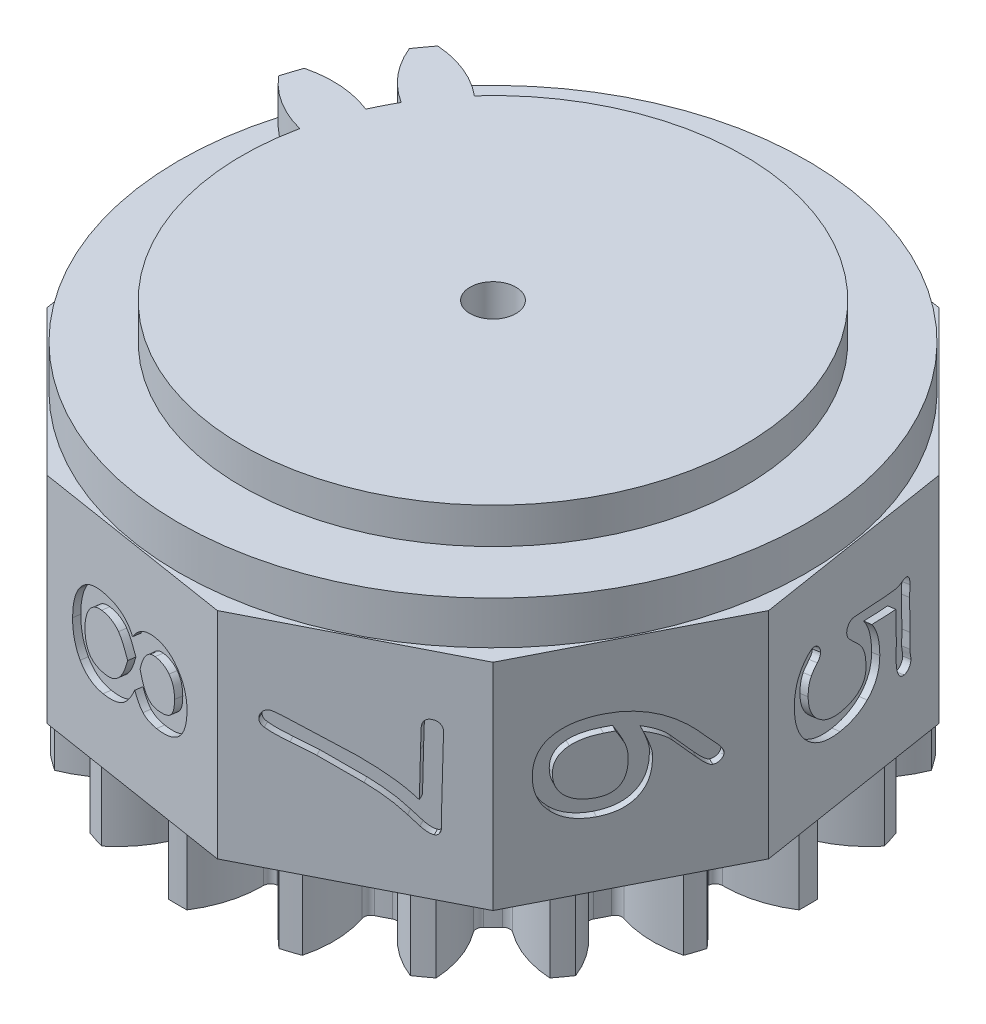
SolidWorks part; units mm, degrees
ref_plane "Front Plane" through (0, 0, 0) normal (0, 0, 1) x (1, 0, 0)
ref_plane "Top Plane" through (0, 0, 0) normal (0, 1, 0) x (1, 0, 0)
ref_plane "Right Plane" through (0, 0, 0) normal (1, 0, 0) x (0, 0, -1)
sketch "Sketch1" plane through (0, 0, 0) normal (0, 1, 0) x (1, 0, 0)
  line L0 (0, 0) -> (0, 59.8949) construction
  line L1 (0, 0) -> (3.1384, 39.8767) construction
  circle A0 centre (0, 0) radius 44
  circle A1 centre (0, 0) radius 37.59 construction
  circle A2 centre (0, 0) radius 40 construction
  circle A3 centre (0, 0) radius 35
  arc A4 (3.6535, 34.8088) -> (0, 45.7006) centre (-11.3105, 35.848) ccw
  arc A5 (-3.6535, 34.8088) -> (0, 45.7006) centre (11.3105, 35.848) cw
  arc A6 (14.2311, 31.9762) -> (14.1222, 43.4638) centre (0.3207, 37.5886) ccw
  arc A7 (7.2819, 34.2341) -> (14.1222, 43.4638) centre (21.8346, 30.5984) cw
  arc A8 (23.4158, 26.0135) -> (26.8621, 36.9725) centre (11.9205, 35.6498) ccw
  arc A9 (17.5044, 30.3084) -> (26.8621, 36.9725) centre (30.2213, 22.3535) cw
  arc A10 (30.3084, 17.5044) -> (36.9725, 26.8621) centre (22.3535, 30.2213) ccw
  arc A11 (26.0135, 23.4158) -> (36.9725, 26.8621) centre (35.6498, 11.9205) cw
  arc A12 (34.2341, 7.2819) -> (43.4638, 14.1222) centre (30.5984, 21.8346) ccw
  arc A13 (31.9762, 14.2311) -> (43.4638, 14.1222) centre (37.5886, 0.3207) cw
  arc A14 (34.8088, -3.6535) -> (45.7006, 0) centre (35.848, 11.3105) ccw
  arc A15 (34.8088, 3.6535) -> (45.7006, 0) centre (35.848, -11.3105) cw
  arc A16 (31.9762, -14.2311) -> (43.4638, -14.1222) centre (37.5886, -0.3207) ccw
  arc A17 (34.2341, -7.2819) -> (43.4638, -14.1222) centre (30.5984, -21.8346) cw
  arc A18 (26.0135, -23.4158) -> (36.9725, -26.8621) centre (35.6498, -11.9205) ccw
  arc A19 (30.3084, -17.5044) -> (36.9725, -26.8621) centre (22.3535, -30.2213) cw
  arc A20 (17.5044, -30.3084) -> (26.8621, -36.9725) centre (30.2213, -22.3535) ccw
  arc A21 (23.4158, -26.0135) -> (26.8621, -36.9725) centre (11.9205, -35.6498) cw
  arc A22 (7.2819, -34.2341) -> (14.1222, -43.4638) centre (21.8346, -30.5984) ccw
  arc A23 (14.2311, -31.9762) -> (14.1222, -43.4638) centre (0.3207, -37.5886) cw
  arc A24 (-3.6535, -34.8088) -> (0, -45.7006) centre (11.3105, -35.848) ccw
  arc A25 (3.6535, -34.8088) -> (0, -45.7006) centre (-11.3105, -35.848) cw
  arc A26 (-14.2311, -31.9762) -> (-14.1222, -43.4638) centre (-0.3207, -37.5886) ccw
  arc A27 (-7.2819, -34.2341) -> (-14.1222, -43.4638) centre (-21.8346, -30.5984) cw
  arc A28 (-23.4158, -26.0135) -> (-26.8621, -36.9725) centre (-11.9205, -35.6498) ccw
  arc A29 (-17.5044, -30.3084) -> (-26.8621, -36.9725) centre (-30.2213, -22.3535) cw
  arc A30 (-30.3084, -17.5044) -> (-36.9725, -26.8621) centre (-22.3535, -30.2213) ccw
  arc A31 (-26.0135, -23.4158) -> (-36.9725, -26.8621) centre (-35.6498, -11.9205) cw
  arc A32 (-34.2341, -7.2819) -> (-43.4638, -14.1222) centre (-30.5984, -21.8346) ccw
  arc A33 (-31.9762, -14.2311) -> (-43.4638, -14.1222) centre (-37.5886, -0.3207) cw
  arc A34 (-34.8088, 3.6535) -> (-45.7006, 0) centre (-35.848, -11.3105) ccw
  arc A35 (-34.8088, -3.6535) -> (-45.7006, 0) centre (-35.848, 11.3105) cw
  arc A36 (-31.9762, 14.2311) -> (-43.4638, 14.1222) centre (-37.5886, 0.3207) ccw
  arc A37 (-34.2341, 7.2819) -> (-43.4638, 14.1222) centre (-30.5984, 21.8346) cw
  arc A38 (-26.0135, 23.4158) -> (-36.9725, 26.8621) centre (-35.6498, 11.9205) ccw
  arc A39 (-30.3084, 17.5044) -> (-36.9725, 26.8621) centre (-22.3535, 30.2213) cw
  arc A40 (-17.5044, 30.3084) -> (-26.8621, 36.9725) centre (-30.2213, 22.3535) ccw
  arc A41 (-23.4158, 26.0135) -> (-26.8621, 36.9725) centre (-11.9205, 35.6498) cw
  arc A42 (-7.2819, 34.2341) -> (-14.1222, 43.4638) centre (-21.8346, 30.5984) ccw
  arc A43 (-14.2311, 31.9762) -> (-14.1222, 43.4638) centre (-0.3207, 37.5886) cw
  circle A44 centre (0, 0) radius 3.2
  dimension "D1" = 88
  dimension "D2" = 80
  dimension "D3" = 75.18
  dimension "D4" = 70
  dimension "D5" = 4.5
  dimension "D6" = 15
  dimension "D8" = 6.4
  dimension "D7" = 20
extrude "Boss-Extrude1" add sketch "Sketch1" along normal mid plane 10 contours A3 | A37 A3 A36 A0 | A35 A3 A34 A0 | A33 A3 A32 A0 | A31 A3 A30 A0 | A29 A3 A28 A0 | A27 A3 A26 A0 | A25 A3 A24 A0 | A23 A3 A22 A0 | A21 A3 A20 A0 | A19 A3 A18 A0 | A17 A3 A16 A0 | A15 A3 A14 A0 | A13 A3 A12 A0 | A11 A3 A10 A0 | A9 A3 A8 A0 | A7 A3 A6 A0 | A5 A3 A4 A0 | A43 A3 A42 A0 | A41 A3 A40 A0 | A39 A3 A38 A0
sketch "Sketch2" plane through (0, 5, 0) normal (0, 1, 0) x (1, 0, 0)
  line L1 (0, 0) -> (-26.7829, 52.5645) construction
  line L11 (-32.7138, 32.7138) -> (-7.2373, 45.6947)
  line L12 (-7.2373, 45.6947) -> (21.0036, 41.2218)
  line L13 (21.0036, 41.2218) -> (41.2218, 21.0036)
  line L14 (41.2218, 21.0036) -> (45.6947, -7.2373)
  line L15 (45.6947, -7.2373) -> (32.7138, -32.7138)
  line L16 (32.7138, -32.7138) -> (7.2373, -45.6947)
  line L17 (7.2373, -45.6947) -> (-21.0036, -41.2218)
  line L18 (-21.0036, -41.2218) -> (-41.2218, -21.0036)
  line L19 (-41.2218, -21.0036) -> (-45.6947, 7.2373)
  line L20 (-45.6947, 7.2373) -> (-32.7138, 32.7138)
  circle A1 centre (0, 0) radius 44 construction
  arc A2 (-14.2311, 31.9762) -> (-17.5044, 30.3084) centre (0, 0) ccw construction
  circle A3 centre (0, 0) radius 3.2 construction
  circle A4 centre (0, 0) radius 3.2
  point P2 (-19.9756, 39.2043)
  point P7 (-15.8897, 31.1852)
  dimension "D1" = 88
  dimension "D2" = 10
extrude "Boss-Extrude2" add sketch "Sketch2" along normal blind 30
sketch "Sketch3" plane through (0, 35, 0) normal (0, 1, 0) x (1, 0, 0)
  line L0 (0, 0) -> (-49.8964, 25.4235) construction
  circle A2 centre (0, 0) radius 3.2
  circle A3 centre (0, 0) radius 3.2
  circle A4 centre (0, 0) radius 35
  arc A5 (-30.3084, 17.5044) -> (-31.9762, 14.2311) centre (0, 0) ccw
  circle A8 centre (-49.8964, 25.4235) radius 19.1 construction
  arc A9 (-41.1947, 14.8808) -> (-36.2525, 24.5805) centre (0, 0) ccw
  arc A35 (-31.9762, 14.2311) -> (-43.4638, 14.1222) centre (-37.5886, 0.3207) ccw construction
  arc A46 (-36.9725, 26.8621) -> (-30.3084, 17.5044) centre (-22.3535, 30.2213) ccw construction
  arc A75 (-31.9762, 14.2311) -> (-41.4288, 14.8208) centre (-37.5886, 0.3207) ccw
  arc A78 (-41.4288, 14.8208) -> (-42.228, 12.3609) centre (0, 0) ccw
  arc A80 (-34.8212, 26.8976) -> (-36.3415, 24.8051) centre (0, 0) ccw
  arc A88 (-36.3415, 24.8051) -> (-30.3084, 17.5044) centre (-22.3535, 30.2213) ccw
  point P0 (-31.1852, 15.8897)
  dimension "D1" = 0
  dimension "D4" = 38.2
  dimension "D5" = 87.6
  dimension "D3" = 56
  dimension "D2" = 0
extrude "Boss-Extrude3" add sketch "Sketch3" along normal blind 6
fillet "Fillet1" radius 1 40 edges at (14.2311, 0, -31.9762) (7.2819, 0, -34.2341) (3.6535, 0, -34.8088) (-3.6535, 0, -34.8088) (-7.2819, 0, -34.2341) (-17.5044, 0, -30.3084) (-14.2311, 0, -31.9762) (-26.0135, 0, -23.4158) (-23.4158, 0, -26.0135) (-30.3084, 0, -17.5044) (-31.9762, 0, -14.2311) (-34.2341, 0, -7.2819) (-34.8088, 0, -3.6535) (-34.8088, 0, 3.6535) (-34.2341, 0, 7.2819) (-31.9762, 0, 14.2311) (-30.3084, 0, 17.5044) (-26.0135, 0, 23.4158) (-23.4158, 0, 26.0135) (-17.5044, 0, 30.3084) (-14.2311, 0, 31.9762) (3.6535, 0, 34.8088) (-7.2819, 0, 34.2341) (-3.6535, 0, 34.8088) (7.2819, 0, 34.2341) (17.5044, 0, 30.3084) (14.2311, 0, 31.9762) (26.0135, 0, 23.4158) (23.4158, 0, 26.0135) (31.9762, 0, 14.2311) (30.3084, 0, 17.5044) (34.2341, 0, 7.2819) (34.8088, 0, 3.6535) (17.5044, 0, -30.3084) (26.0135, 0, -23.4158) (31.9762, 0, -14.2311) (34.8088, 0, -3.6535) (23.4158, 0, -26.0135) (34.2341, 0, -7.2819) (30.3084, 0, -17.5044)
sketch "Sketch4" plane through (0, 41, 0) normal (0, 1, 0) x (1, 0, 0)
  arc A0 (-30.3084, 17.5044) -> (-31.9762, 14.2311) centre (0, 0) ccw
  arc A1 (-34.58, 26.8824) -> (-36.2525, 24.5805) centre (0, 0) ccw
  arc A6 (-36.3415, 24.8051) -> (-30.3084, 17.5044) centre (-22.3535, 30.2213) ccw construction
  arc A7 (-30.3084, 17.5044) -> (-31.9762, 14.2311) centre (0, 0) ccw construction
  arc A8 (-31.9762, 14.2311) -> (-41.4288, 14.8208) centre (-37.5886, 0.3207) ccw construction
  arc A10 (-34.58, 26.8824) -> (-36.2525, 24.5805) centre (0, 0) ccw
  arc A18 (-36.2525, 24.5805) -> (-30.3084, 17.5044) centre (-22.3535, 30.2213) ccw
  arc A19 (-30.3084, 17.5044) -> (-31.9762, 14.2311) centre (0, 0) ccw
  arc A20 (-31.9762, 14.2311) -> (-41.1947, 14.8808) centre (-37.5886, 0.3207) ccw
  circle A28 centre (0, 0) radius 35
  arc A29 (-34.2341, 7.2819) -> (-26.0135, 23.4158) centre (0, 0) ccw
  arc A35 (-41.1947, 14.8808) -> (-36.2525, 24.5805) centre (0, 0) ccw
  arc A37 (-36.2525, 24.5805) -> (-30.3084, 17.5044) centre (-22.3535, 30.2213) ccw
  arc A39 (-30.3084, 17.5044) -> (-31.9762, 14.2311) centre (0, 0) ccw
  arc A41 (-31.9762, 14.2311) -> (-41.1947, 14.8808) centre (-37.5886, 0.3207) ccw
  arc A43 (-41.1947, 14.8808) -> (-42.0739, 12.1748) centre (0, 0) ccw
  arc A45 (-36.2525, 24.5805) -> (-30.3084, 17.5044) centre (-22.3535, 30.2213) ccw
  arc A47 (-30.3084, 17.5044) -> (-31.9762, 14.2311) centre (0, 0) ccw
  arc A49 (-31.9762, 14.2311) -> (-41.1947, 14.8808) centre (-37.5886, 0.3207) ccw
  arc A59 (-31.9762, 14.2311) -> (-43.4638, 14.1222) centre (-37.5886, 0.3207) ccw construction
  arc A60 (-43.4638, 14.1222) -> (-34.2341, 7.2819) centre (-30.5984, 21.8346) ccw construction
  arc A69 (-26.0135, 23.4158) -> (-36.9725, 26.8621) centre (-35.6498, 11.9205) ccw construction
  arc A70 (-36.9725, 26.8621) -> (-30.3084, 17.5044) centre (-22.3535, 30.2213) ccw construction
  arc A99 (-31.9762, 14.2311) -> (-41.1947, 14.8808) centre (-37.5886, 0.3207) ccw
  arc A100 (-42.0739, 12.1748) -> (-34.2341, 7.2819) centre (-30.5984, 21.8346) ccw
  arc A109 (-26.0135, 23.4158) -> (-34.58, 26.8824) centre (-35.6498, 11.9205) ccw
  arc A110 (-36.2525, 24.5805) -> (-30.3084, 17.5044) centre (-22.3535, 30.2213) ccw
  arc M3 (-36.2525, 24.5805) -> (-30.3084, 17.5044) centre (-22.3535, 30.2213) ccw
  arc M5 (-30.3084, 17.5044) -> (-31.9762, 14.2311) centre (0, 0) ccw
  arc M7 (-31.9762, 14.2311) -> (-41.1947, 14.8808) centre (-37.5886, 0.3207) ccw
  circle M8 centre (0, 0) radius 3.2
  arc M30 (-41.1947, 14.8808) -> (-36.2525, 24.5805) centre (0, 0) ccw
  dimension "D1" = 0
  dimension "D3" = 0
extrude "Boss-Extrude4" add sketch "Sketch4" along normal blind 5 contours A29 A109 A100 M30 M3 M5 M7 M8
sketch "Sketch7" plane through (-43.4583, 0, 6.8831) normal (-0.9877, 0, 0.1564) x (0.1564, 0, 0.9877)
  line L1 (-9.2965, 35) -> (-9.2965, 5) construction
  line L2 (-14.2965, 35) -> (14.2965, 35) construction
  line L3 (-14.2965, 5) -> (14.2965, 5) construction
  line L4 (9.2965, 35) -> (9.2965, 5) construction
  line L5 (-14.2965, 35) -> (-14.2965, 5) construction
  line L7 (14.2965, 35) -> (14.2965, 5) construction
  text T0 "0" font "Comic Sans MS" height 18.5
  dimension "D1" = 5
  dimension "D2" = 5
sketch "Sketch8" plane through (-31.1127, 0, 31.1127) normal (-0.7071, 0, 0.7071) x (0.7071, 0, 0.7071)
  line L0 (-9.2965, 34.9886) -> (-9.2965, 4.9886) construction
  line L1 (9.7762, 34.9886) -> (9.7762, 4.9886) construction
  line L2 (-14.2965, 35) -> (-14.2965, 5) construction
  text T0 "9" font "Comic Sans MS" height 18.5
  dimension "D1" = 5
sketch "Sketch9" plane through (-6.8831, 0, 43.4583) normal (-0.1564, 0, 0.9877) x (0.9877, 0, 0.1564)
  line L0 (-9.2965, 35) -> (-9.2965, 5) construction
  line L1 (-14.2965, 35) -> (14.2965, 35) construction
  line L2 (-8.1575, 5) -> (-5.6028, 5) construction
  line L3 (-14.2965, 35) -> (-14.2965, 5) construction
  text T0 "8" font "Comic Sans MS" height 18.5
  dimension "D1" = 5
sketch "Sketch10" plane through (19.9756, 0, 39.2043) normal (0.454, 0, 0.891) x (0.891, 0, -0.454)
  line L0 (-9.2965, 35) -> (-9.2965, 5) construction
  line L1 (-14.2965, 35) -> (14.2965, 35) construction
  line L2 (-5.6028, 5) -> (-1.9418, 5) construction
  line L3 (-14.2965, 35) -> (-14.2965, 5) construction
  text T0 "7" font "Comic Sans MS" height 18.5
  dimension "D1" = 5
sketch "Sketch11" plane through (39.2043, 0, 19.9756) normal (0.891, 0, 0.454) x (0.454, 0, -0.891)
  line L0 (-9.2965, 35) -> (-9.2965, 5) construction
  line L1 (-14.2965, 35) -> (14.2965, 35) construction
  line L2 (-14.2965, 5) -> (14.2965, 5) construction
  line L3 (-14.2965, 35) -> (-14.2965, 5) construction
  text T0 "6" font "Comic Sans MS" height 18.5
  dimension "D1" = 5
sketch "Sketch12" plane through (43.4583, 0, -6.8831) normal (0.9877, 0, -0.1564) x (-0.1564, 0, -0.9877)
  line L0 (-9.2965, 35) -> (-9.2965, 5) construction
  text T0 "5" font "Comic Sans MS" height 18.5
sketch "Sketch13" plane through (31.1127, 0, -31.1127) normal (0.7071, 0, -0.7071) x (-0.7071, 0, -0.7071)
  line L0 (-9.7762, 34.9886) -> (-9.7762, 4.9886) construction
  line L1 (-9.7762, 34.9886) -> (-9.7762, 4.9886) construction
  text T0 "4" font "Comic Sans MS" height 18.5
sketch "Sketch14" plane through (6.8831, 0, -43.4583) normal (0.1564, 0, -0.9877) x (-0.9877, 0, -0.1564)
  line L1 (-9.2965, 35) -> (-9.2965, 5) construction
  line L2 (-14.2965, 35) -> (-14.2965, 5) construction
  text T0 "3" font "Comic Sans MS" height 18.5
  dimension "D1" = 5
sketch "Sketch15" plane through (-19.9756, 0, -39.2043) normal (-0.454, 0, -0.891) x (-0.891, 0, 0.454)
  line L0 (-9.2965, 35) -> (-9.2965, 5) construction
  line L5 (-14.2965, 35) -> (14.2965, 35) construction
  line L6 (-14.2965, 5) -> (14.2965, 5) construction
  line L7 (-14.2965, 35) -> (-14.2965, 5) construction
  text T0 "2" font "Comic Sans MS" height 18.5
  dimension "D1" = 5
sketch "Sketch16" plane through (-39.2043, 0, -19.9756) normal (-0.891, 0, -0.454) x (-0.454, 0, 0.891)
  line L0 (-9.2965, 35) -> (-9.2965, 5) construction
  line L1 (-14.2965, 35) -> (14.2965, 35) construction
  line L2 (-14.2965, 5) -> (14.2965, 5) construction
  line L3 (-14.2965, 35) -> (-14.2965, 5) construction
  text T0 "1" font "Comic Sans MS" height 18.5
  dimension "D1" = 5
extrude "Cut-Extrude1" cut sketch "Sketch7" against normal blind 1
extrude "Cut-Extrude2" cut sketch "Sketch16" against normal blind 1
extrude "Cut-Extrude3" cut sketch "Sketch15" against normal blind 1
extrude "Cut-Extrude4" cut sketch "Sketch14" against normal blind 1
extrude "Cut-Extrude5" cut sketch "Sketch13" against normal blind 1
extrude "Cut-Extrude6" cut sketch "Sketch12" against normal blind 1
extrude "Cut-Extrude7" cut sketch "Sketch11" against normal blind 1
extrude "Cut-Extrude8" cut sketch "Sketch10" against normal blind 1
extrude "Cut-Extrude9" cut sketch "Sketch8" against normal blind 1
extrude "Cut-Extrude10" cut sketch "Sketch9" against normal blind 1
extrude "Cut-Extrude11" cut sketch "Sketch17" against normal blind 40
sketch "Sketch17" plane through (-340.7728, -18, -1096.3282) normal (0, -1, 0) x (0.942, 0, 0.3357)
  circle A0 centre (697.367, 931.3924) radius 3.2
